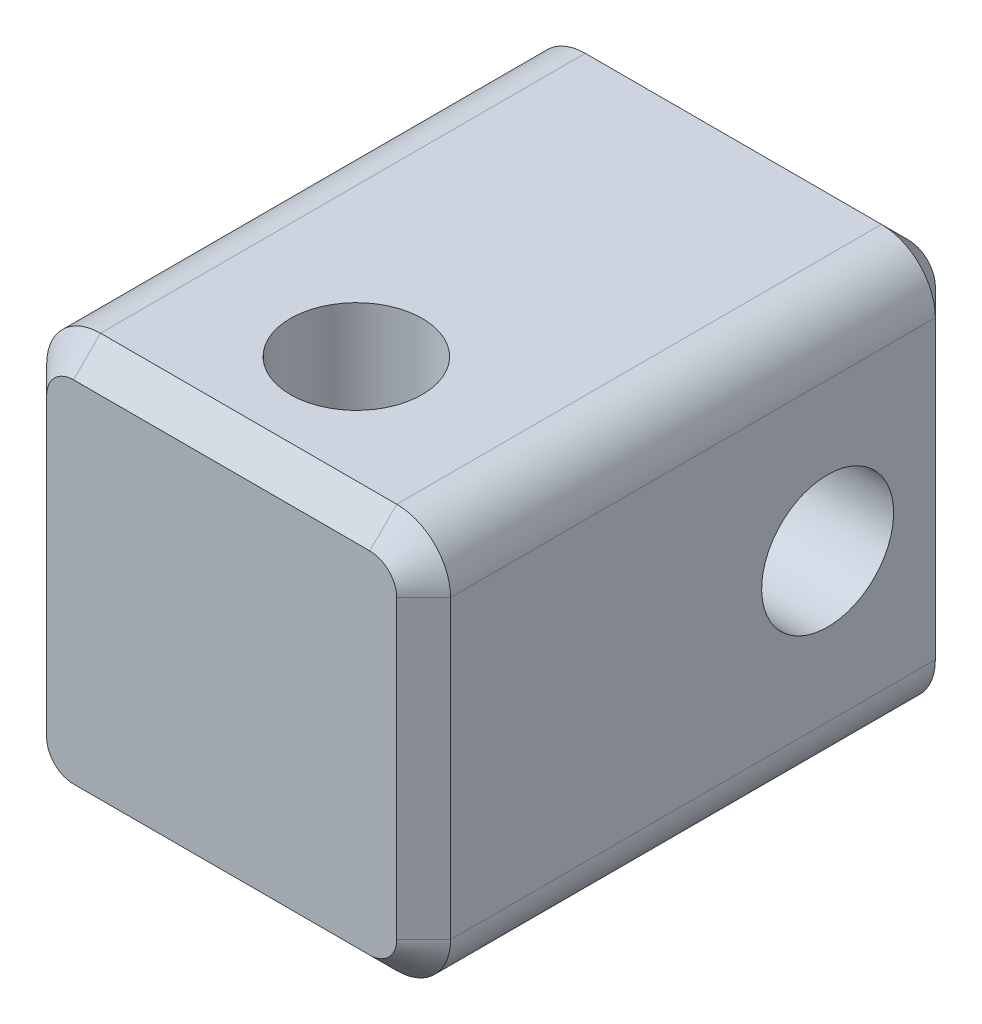
SolidWorks part; units mm, degrees
ref_plane "正面(Front)" through (0, 0, 0) normal (0, 0, 1) x (1, 0, 0)
ref_plane "平面(Top)" through (0, 0, 0) normal (0, 1, 0) x (1, 0, 0)
ref_plane "右側面(Right)" through (0, 0, 0) normal (1, 0, 0) x (0, 0, -1)
sketch "ｽｹｯﾁ1" plane through (0, 0, 0) normal (0, 0, 1) x (1, 0, 0)
  line L1 (-7.5, 7.5) -> (7.5, 7.5)
  line L2 (-7.5, 7.5) -> (-7.5, -7.5)
  line L3 (-7.5, -7.5) -> (7.5, -7.5)
  line L4 (7.5, 7.5) -> (7.5, -7.5)
  line L5 (-7.5, 7.5) -> (7.5, -7.5) construction
  line L6 (-7.5, -7.5) -> (7.5, 7.5) construction
  point P0 (0, 0)
  dimension "D1" = 15
  dimension "D2" = 15
extrude "ﾎﾞｽ - 押し出し1" add sketch "ｽｹｯﾁ1" along normal blind 20
sketch "ｽｹｯﾁ2" plane through (7.5, 0, 0) normal (1, 0, 0) x (0, 0, -1)
  line L0 (0, 0) -> (-23.2092, 0) construction
  line L1 (0, -7.5) -> (0, 7.5) construction
  circle A0 centre (-5, 0) radius 2.45
  dimension "D1" = 5
  dimension "D2" = 4.9
extrude "ｶｯﾄ - 押し出し1" cut sketch "ｽｹｯﾁ2" against normal through all
sketch "ｽｹｯﾁ3" plane through (0, 7.5, 0) normal (0, 1, 0) x (1, 0, 0)
  line L0 (0, 0) -> (0, -20) construction
  line L1 (7.5, -20) -> (-7.5, -20) construction
  circle A0 centre (0, -15) radius 2.45
  dimension "D1" = 4.9
  dimension "D2" = 5
extrude "ｶｯﾄ - 押し出し2" cut sketch "ｽｹｯﾁ3" against normal through all
fillet "ﾌｨﾚｯﾄ1" radius 2 4 edges at (7.5, -7.5, 10) (-7.5, -7.5, 10) (-7.5, 7.5, 10) (7.5, 7.5, 10)
chamfer "面取り1" distance 1 angle 45 16 edges at (-6.9142, -6.9142, 20) (-7.5, 0, 20) (-6.9142, 6.9142, 20) (0, 7.5, 20) (6.9142, 6.9142, 20) (7.5, 0, 20) (6.9142, -6.9142, 20) (0, -7.5, 20) (6.9142, 6.9142, 0) (0, 7.5, 0) (-6.9142, 6.9142, 0) (-7.5, 0, 0) (-6.9142, -6.9142, 0) (0, -7.5, 0) (6.9142, -6.9142, 0) (7.5, 0, 0)
